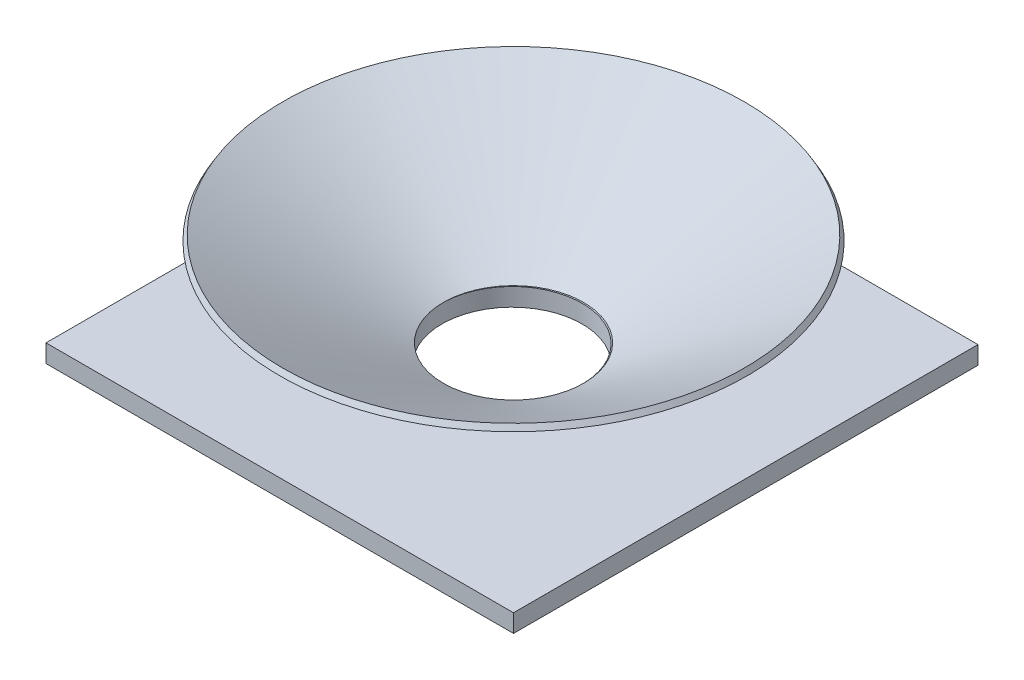
SolidWorks part; units mm, degrees
ref_plane "Front Plane" through (0, 0, 0) normal (0, 0, 1) x (1, 0, 0)
ref_plane "Top Plane" through (0, 0, 0) normal (0, 1, 0) x (1, 0, 0)
ref_plane "Right Plane" through (0, 0, 0) normal (1, 0, 0) x (0, 0, -1)
sketch "Sketch1" plane through (0, 0, 0) normal (0, 0, 1) x (1, 0, 0)
  line L0 (-13.7069, 0) -> (-39.075, 14.7607)
  line L1 (-39.075, 14.7607) -> (-38.5721, 15.625)
  line L2 (-38.5721, 15.625) -> (-11.7185, 0)
  line L3 (-13.7069, 0) -> (-11.7185, 0)
  line L4 (0, 0) -> (0, 38.049) construction
  line L5 (0, 0) -> (-37.9362, 0) construction
  dimension "D1" = 11.7185
  dimension "D2" = 39.075
  dimension "D3" = 1
  dimension "D4" = 15.625
revolve "Revolve1" add sketch "Sketch1" angle 360 about L4
sketch "Sketch2" plane through (0, 0, 0) normal (0, 1, 0) x (1, 0, 0)
  line L0 (-39.075, -39.075) -> (39.075, -39.075)
  line L1 (-39.075, -39.075) -> (-39.075, 38.5721)
  line L2 (39.075, -39.075) -> (39.075, 38.5721)
  line L3 (-39.075, 38.5721) -> (39.075, 38.5721)
  line L4 (-39.075, -39.075) -> (39.075, 38.5721) construction
  line L5 (39.075, -39.075) -> (-39.075, 38.5721) construction
  circle A0 centre (0, -0.2515) radius 11.72
  circle A1 centre (0, 0) radius 39.075 construction
  circle A2 centre (0, 0) radius 38.5721 construction
  point P1 (0, -0.2515)
  point P3 (169.0258, -154.8303)
  dimension "D1" = 23.44
extrude "Boss-Extrude1" add sketch "Sketch2" against normal blind 3 separate body
